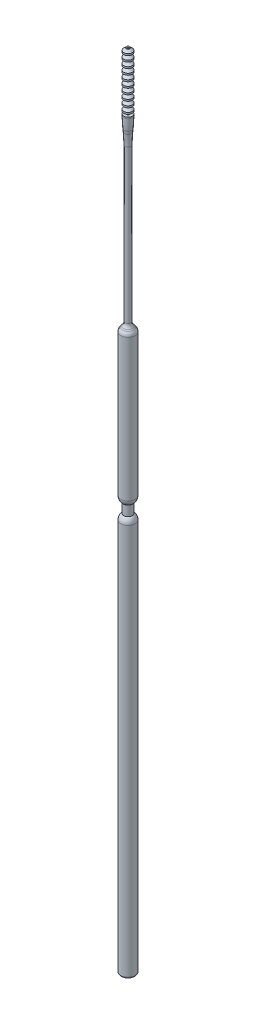
SolidWorks part; units mm, degrees
ref_plane "Front Plane" through (0, 0, 0) normal (0, 0, 1) x (1, 0, 0)
ref_plane "Top Plane" through (0, 0, 0) normal (0, 1, 0) x (1, 0, 0)
ref_plane "Right Plane" through (0, 0, 0) normal (1, 0, 0) x (0, 0, -1)
sketch "Sketch2" plane through (0, 0, 0) normal (0, 1, 0) x (1, 0, 0)
  circle A0 centre (0, 0) radius 0.5
  dimension "D1" = 1
extrude "Boss-Extrude1" add sketch "Sketch2" along normal blind 5
sketch "Sketch4" plane through (0, 0, 0) normal (1, 0, 0) x (0, 0, -1)
  line L0 (0, 5) -> (0, 10.5)
  line L1 (0.5, 5) -> (-0.5, 5) construction
  line L2 (0, 10.5) -> (0.75, 10.5)
  line L3 (0.75, 10.5) -> (0.75, 9)
  line L4 (0.5, 5) -> (0.5, 6.5)
  line L5 (0.5, 6.5) -> (0.75, 9)
  line L6 (0, 5) -> (0.5, 5)
  point P5 (0.75, 9)
  point P7 (0.5, 6.5)
  dimension "D1" = 5.5
  dimension "D2" = 0.75
  dimension "D3" = 1.5
  dimension "D4" = 1.5
  dimension "D5" = 0.5
revolve "Revolve1" add sketch "Sketch4" angle 360 about L0
fillet "Fillet1" radius 20 2 edges at (0, 9, -0.75) (0, 6.5, -0.5)
sketch "Sketch5" plane through (0, 10.5, 0) normal (0, 1, 0) x (1, 0, 0)
  line L2 (-0.125, 0.7395) -> (-0.125, -0.7395)
  line L4 (0.125, 0.7395) -> (0.125, -0.7395)
  line L5 (-0.7395, 0.125) -> (0.7395, 0.125)
  line L7 (-0.7395, -0.125) -> (0.7395, -0.125)
  circle A0 centre (0, 0) radius 0.75
  circle A1 centre (0, 0) radius 0.5
  circle A2 centre (0, 0) radius 0.25
  dimension "D1" = 1
  dimension "D6" = 1.5
  dimension "0.5" = 0.5
  dimension "D2" = 0.125
  dimension "D3" = 0.25
  dimension "D4" = 0.125
  dimension "D5" = 0.25
extrude "Boss-Extrude3" add sketch "Sketch5" along normal blind 1 contours L4 A2 L2 L5 | L7 A2 L5 L4 | L5 A2 L4 | L4 A2 L7 | L2 A2 L4 L7 | L2 L7 L4 L5 | L5 A2 L7 L2 | L2 A2 L5 | L7 A2 L2
sketch "Sketch10" plane through (0, 0, 0) normal (0, 0, 1) x (1, 0, 0)
  line L0 (0, 11.5) -> (0.75, 10.9748)
  line L1 (0.25, 11.5) -> (-0.25, 11.5) construction
  line L2 (0.75, 10.6697) -> (0.75, 10.9748)
  line L3 (0, 11.1948) -> (0.75, 10.6697)
  line L4 (0, 11.5) -> (0, 11.1948)
  dimension "D1" = 35
  dimension "D2" = 0.25
revolve "Revolve5" add sketch "Sketch10" angle 360 about L4
other "Move Face1" face at (0, 10.5, 0.25) parameters "D1"=0.25
sketch "Sketch8" plane through (0, 0, 0) normal (0, -1, 0) x (-1, 0, 0)
  circle A0 centre (0, 0) radius 0.5
extrude "Boss-Extrude4" add sketch "Sketch8" along normal blind 21.5
sketch "Sketch9" plane through (0, 0, 0) normal (0, 0, 1) x (1, 0, 0)
  line L0 (-0.5, -21.5) -> (-0.5, -22)
  line L1 (-0.5, -22) -> (-1.25, -22.75)
  line L2 (-1.25, -22.75) -> (-1.25, -23.25)
  line L3 (-0.5, 5.5025) -> (-0.5, -21.5) construction
  line L4 (-1.25, -23.25) -> (-1.25, -48.25)
  line L5 (-0.5, -21.5) -> (0, -21.5)
  line L6 (0, -48.25) -> (0, -52)
  line L8 (-1.25, -52) -> (-1.25, -120.25)
  line L9 (-1.25, -120.25) -> (-1.25, -121.5)
  line L10 (0, -21.5) -> (0, -121.5)
  line L11 (-0.5, -21.5) -> (0.5, -21.5) construction
  line L12 (0, -121.5) -> (-1.25, -121.5)
  line L13 (-0.75, -49.25) -> (-0.75, -51)
  arc A1 (-0.75, -51) -> (-1.25, -52) centre (0, -52) ccw
  arc A2 (-1.25, -48.25) -> (-0.75, -49.25) centre (0, -48.25) ccw
  dimension "D7" = 3.75
  dimension "D10" = 0.75
  dimension "D1" = 0.75
  dimension "D2" = 0.5
  dimension "D3" = 0.5
  dimension "D4" = 0.75
  dimension "D5" = 25
  dimension "D6" = 1.25
  dimension "D8" = 68.25
  dimension "D9" = 1.25
  dimension "D11" = 0.75
revolve "Revolve4" add sketch "Sketch9" angle 360 about L10
fillet "Fillet6" radius 0.25 1 edges at (0, -121.5, 1.25)
fillet "Fillet7" radius 1 2 edges at (0, -22.75, 1.25) (0, -22, 0.5)
pattern_linear "LPattern1" count 10 spacing 1 along (0, 1, 0) of "Revolve5", "Boss-Extrude3"
fillet "Fillet8" radius 0.1 2 edges at (0.25, 20.3249, 0) (0, 20.5, 0.25)
